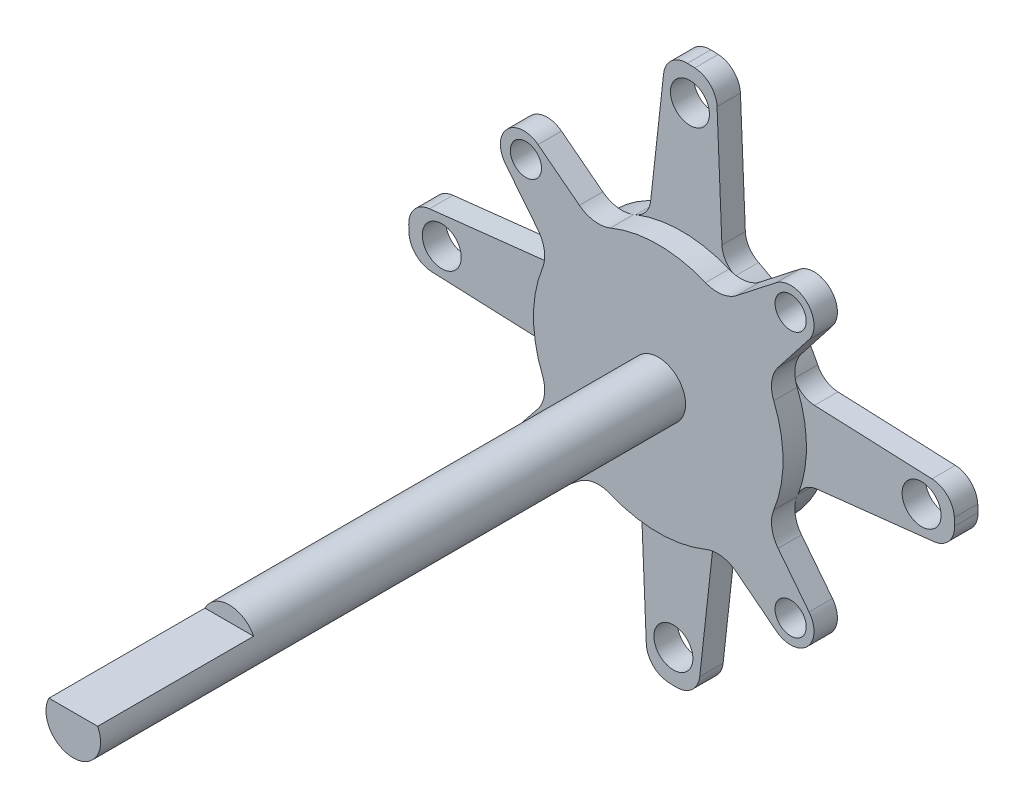
SolidWorks part; units mm, degrees
ref_plane "前视基准面" through (0, 0, 0) normal (0, 0, 1) x (1, 0, 0)
ref_plane "上视基准面" through (0, 0, 0) normal (0, 1, 0) x (1, 0, 0)
ref_plane "右视基准面" through (0, 0, 0) normal (1, 0, 0) x (0, 0, -1)
sketch "草图2" plane through (0, 0, 0) normal (0, 0, 1) x (1, 0, 0)
  circle A13 centre (0, 0) radius 3.5
  dimension "D1" = 7
extrude "凸台-拉伸1" add sketch "草图2" against normal blind 75
sketch "草图3" plane through (0, 0, -75) normal (0, 0, -1) x (-1, 0, 0)
  line L1 (0, 0) -> (6.9127, 0) construction
  line L2 (-19.3332, 15.1218) -> (-7.5, 0)
  line L3 (-7.5, 0) -> (-19.3332, -15.1218)
  line L4 (-15.1218, -19.3332) -> (0, -7.5)
  line L5 (0, -7.5) -> (15.4077, -19.3972)
  line L6 (19.5864, -15.152) -> (7.5, 0)
  line L7 (7.5, 0) -> (19.5864, 15.152)
  line L8 (15.4077, 19.3972) -> (0, 7.5)
  line L9 (0, 7.5) -> (-15.1218, 19.3332)
  line L10 (0, 0) -> (0, 2.4692)
  arc A1 (-15.1218, 19.3332) -> (-19.3332, 15.1218) centre (-16.9706, 16.9706) ccw
  circle A2 centre (-16.9706, 16.9706) radius 2
  arc A3 (19.5864, 15.152) -> (15.4077, 19.3972) centre (17.2412, 17.0227) ccw
  arc A4 (19.5864, -15.152) -> (15.4077, -19.3972) centre (17.2412, -17.0227) cw
  arc A5 (-15.1218, -19.3332) -> (-19.3332, -15.1218) centre (-16.9706, -16.9706) cw
  circle A6 centre (16.9706, 16.9706) radius 2
  circle A7 centre (16.9706, -16.9706) radius 2
  circle A8 centre (-16.9706, -16.9706) radius 2
  dimension "D2" = 6
  dimension "D3" = 6
  dimension "D4" = 4
extrude "凸台-拉伸2" add sketch "草图3" along normal blind 3
fillet "圆角1" radius 5 4 edges at (7.5, 0, -76.5) (0, -7.5, -76.5) (0, 7.5, -76.5) (-7.5, 0, -76.5)
sketch "草图5" plane through (0, 0, -75) normal (0, 0, 1) x (1, 0, 0)
  circle A0 centre (0, 0) radius 16
  dimension "D1" = 32
extrude "凸台-拉伸3" add sketch "草图5" against normal blind 3
fillet "圆角2" radius 4 8 edges at (-8.1321, 13.7793, -76.5) (8.0706, 13.8154, -76.5) (13.8154, 8.0706, -76.5) (13.8154, -8.0706, -76.5) (8.0706, -13.8154, -76.5) (-8.1321, -13.7793, -76.5) (-13.8669, -7.9818, -76.5) (-13.8669, 7.9818, -76.5)
sketch "草图6" plane through (0, 0, -78) normal (0, 0, -1) x (-1, 0, 0)
  line L0 (16.9706, 16.9706) -> (-16.9706, -16.9706) construction
  line L1 (-16.9706, 16.9706) -> (16.9706, -16.9706) construction
  line L2 (-4.5363, 32.0875) -> (-5.2413, 15.1172)
  line L3 (0, 0) -> (-1.0607, 30.7591) construction
  line L4 (2.3152, 32.3238) -> (4.1875, 15.4423)
  line L5 (32.0875, -4.5363) -> (15.1172, -5.2413)
  line L6 (32.3238, 2.3152) -> (15.4423, 4.1875)
  line L7 (-32.3238, -2.3152) -> (-15.4423, -4.1875)
  line L8 (-32.0875, 4.5363) -> (-15.1172, 5.2413)
  line L9 (-2.3152, -32.3238) -> (-4.1875, -15.4423)
  line L10 (4.5363, -32.0875) -> (5.2413, -15.1172)
  circle A2 centre (-1.0607, 30.7591) radius 2.5
  circle A3 centre (30.7591, -1.0607) radius 2.5
  circle A4 centre (1.0607, -30.7591) radius 2.5
  circle A5 centre (-30.7591, 1.0607) radius 2.5
  arc A6 (-15.4423, -4.1875) -> (-4.1875, -15.4423) centre (0, 0) ccw
  arc A7 (-0.729, 34.9924) -> (-1.6831, 34.9595) centre (0, 0) ccw
  arc A8 (-4.5363, 32.0875) -> (-1.6831, 34.9595) centre (-1.5389, 31.963) cw
  arc A9 (2.3152, 32.3238) -> (-0.729, 34.9924) centre (-0.6665, 31.9931) ccw
  arc A10 (32.3238, 2.3152) -> (34.9924, -0.729) centre (31.9931, -0.6665) cw
  arc A11 (34.9924, -0.729) -> (34.9595, -1.6831) centre (0, 0) cw
  arc A12 (32.0875, -4.5363) -> (34.9595, -1.6831) centre (31.963, -1.5389) ccw
  arc A13 (-32.0875, 4.5363) -> (-34.9595, 1.6831) centre (-31.963, 1.5389) ccw
  arc A14 (-32.3238, -2.3152) -> (-34.9924, 0.729) centre (-31.9931, 0.6665) cw
  arc A15 (-34.9924, 0.729) -> (-34.9595, 1.6831) centre (0, 0) cw
  arc A16 (4.5363, -32.0875) -> (1.6831, -34.9595) centre (1.5389, -31.963) cw
  arc A17 (0.729, -34.9924) -> (1.6831, -34.9595) centre (0, 0) ccw
  arc A18 (-2.3152, -32.3238) -> (0.729, -34.9924) centre (0.6665, -31.9931) ccw
  arc A19 (5.2413, -15.1172) -> (15.1172, -5.2413) centre (0, 0) ccw
  arc A20 (15.4423, 4.1875) -> (4.1875, 15.4423) centre (0, 0) ccw
  arc A21 (-5.2413, 15.1172) -> (-15.1172, 5.2413) centre (0, 0) ccw
  point P25 (-4.427, 34.7189)
  point P28 (2.0249, 34.9414)
  dimension "D1" = 5
  dimension "D2" = 22.5
  dimension "D3" = 21
  dimension "D4" = 70
  dimension "D5" = 3
  dimension "D6" = 3
extrude "凸台-拉伸4" add sketch "草图6" along normal blind 3
fillet "圆角3" radius 3 1 edges at (5.2413, 15.1172, -79.5)
fillet "圆角4" radius 3 7 edges at (15.1172, 5.2413, -79.5) (15.4423, -4.1875, -79.5) (4.1875, -15.4423, -79.5) (-5.2413, -15.1172, -79.5) (-15.1172, -5.2413, -79.5) (-15.4423, 4.1875, -79.5) (-4.1875, 15.4423, -79.5)
sketch "草图7" plane through (0, 0, 0) normal (0, 0, 1) x (1, 0, 0)
  line L0 (0, 0) -> (0, 3.5)
  circle A0 centre (0, 0) radius 3.5 construction
ref_plane "基准面1" through (0, 3.5, 0) normal (0, 1, 0) x (1, 0, 0)
sketch "草图8" plane through (0, 0, 0) normal (0, 0, 1) x (1, 0, 0)
  line L0 (-3.124, 1.5781) -> (3.124, 1.5781)
  line L1 (-3.124, 1.5781) -> (-3.124, 4.393)
  line L2 (-3.124, 4.393) -> (3.2505, 4.2179)
  line L3 (3.2505, 4.2179) -> (3.124, 1.5781)
  circle A2 centre (0, 0) radius 3.5 construction
  point P6 (3.2505, 4.2179)
extrude "切除-拉伸1" cut sketch "草图8" against normal blind 20 contours L1 L2 L3 L0
